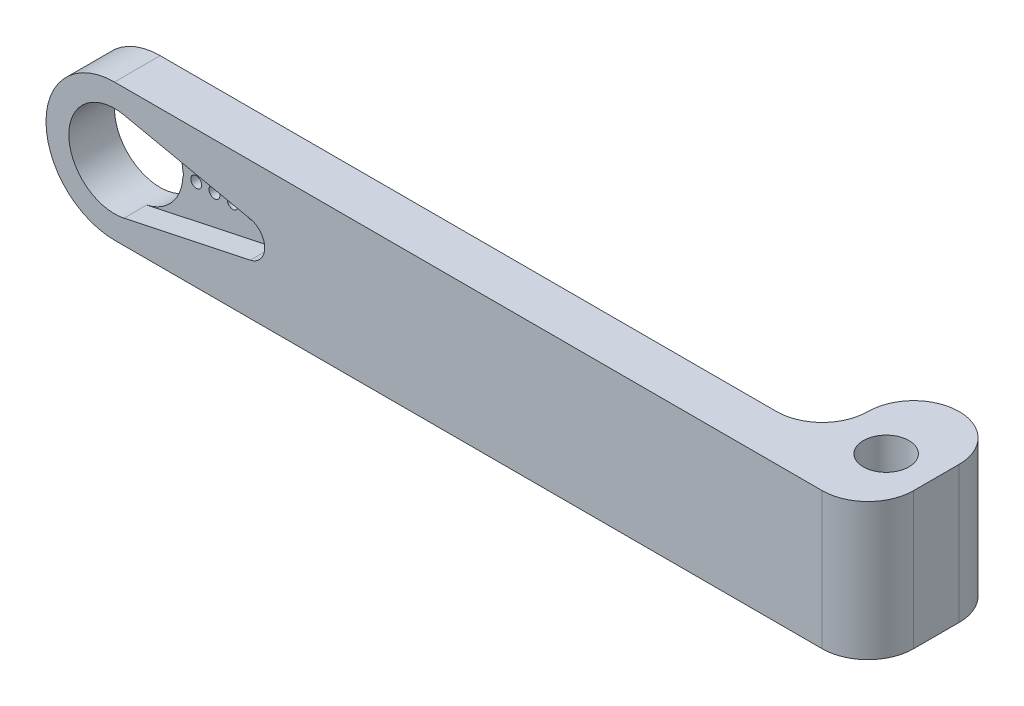
SolidWorks part; units mm, degrees
note: '?' marks a value the reader was unsure of.
ref_plane "Front Plane" through (0, 0, 0) normal (0, 0, 1) x (1, 0, 0)
ref_plane "Top Plane" through (0, 0, 0) normal (0, 1, 0) x (1, 0, 0)
ref_plane "Right Plane" through (0, 0, 0) normal (1, 0, 0) x (0, 0, -1)
sketch "Sketch1" plane through (0, 0, 0) normal (0, 0, 1) x (1, 0, 0)
  line L0 (0, 0) -> (75, 0) construction
  line L1 (0, 7.5) -> (75, 7.5)
  line L2 (0, -7.5) -> (75, -7.5)
  arc A0 (0, 7.5) -> (0, -7.5) centre (0, 0) ccw
  arc A1 (75, -7.5) -> (75, 7.5) centre (75, 0) ccw
  circle A2 centre (0, 0) radius 5
  circle A3 centre (75, 0) radius 2.5
  point P3 (37.5, 0)
  dimension "D1" = 10
  dimension "D2" = 7.5
  dimension "D4" = 5
  dimension "D3" = 75
extrude "Boss-Extrude1" add sketch "Sketch1" along normal blind 5
sketch "Sketch2" plane through (0, 0, 5) normal (0, 0, 1) x (1, 0, 0)
  line L0 (0, 0) -> (4.45, 0) construction
  circle A0 centre (4.45, 0) radius 0.6
  circle A1 centre (6.45, 0) radius 0.6
  circle A2 centre (8.45, 0) radius 0.6
  circle A3 centre (10.45, 0) radius 0.6
  circle A4 centre (12.45, 0) radius 0.6
  circle A5 centre (14.45, 0) radius 0.6
  dimension "D1" = 1.2
  dimension "D2" = 4.45
  dimension "D4" = 2
  dimension "D3" = 6
extrude "Cut-Extrude1" cut sketch "Sketch2" against normal through all
sketch "Sketch3" plane through (0, 0, 5) normal (0, 0, 1) x (1, 0, 0)
  line L0 (1.0381, 4.8911) -> (14.8652, 1.9564)
  line L1 (0, 0) -> (14.45, 0) construction
  line L2 (1.0381, -4.8911) -> (14.8652, -1.9564)
  circle A0 centre (0, 0) radius 5
  circle A1 centre (14.45, 0) radius 2
  arc A2 (4.9935, 0.2541) -> (4.9935, -0.2541) centre (0, 0) ccw construction
  dimension "D1" = 4
extrude "Cut-Extrude2" cut sketch "Sketch3" against normal blind 2.5
sketch "Sketch4" plane through (0, 7.5, 0) normal (0, 1, 0) x (1, 0, 0)
  line L1 (82.5, -5) -> (72.5, -5)
  line L2 (82.5, -5) -> (82.5, 10)
  line L3 (82.5, 10) -> (72.5, 10)
  line L4 (72.5, -5) -> (72.5, 10)
  dimension "D1" = 10
  dimension "D2" = 15
extrude "Boss-Extrude2" add sketch "Sketch4" against normal blind 15
sketch "Sketch5" plane through (0, 7.5, 0) normal (0, 1, 0) x (1, 0, 0)
  line L0 (77.5, 10) -> (77.5, 2) construction
  line L1 (82.5, 10) -> (72.5, 10) construction
  line L2 (77.5, 2) -> (77.5, -5) construction
  line L3 (82.5, -5) -> (0, -5) construction
  circle A0 centre (77.5, 2) radius 2.5
  dimension "D1" = 5
  dimension "D2" = 7
extrude "Cut-Extrude3" cut sketch "Sketch5" against normal blind 15 contours A0
ref_axis "Axis1" through (77.5, -7.5, -2) along (0, 1, 0)?
fillet "Fillet1" radius 5 4 edges at (82.5, 0, -10) (72.5, 0, -10) (72.5, 0, 0) (82.5, 0, 5)
